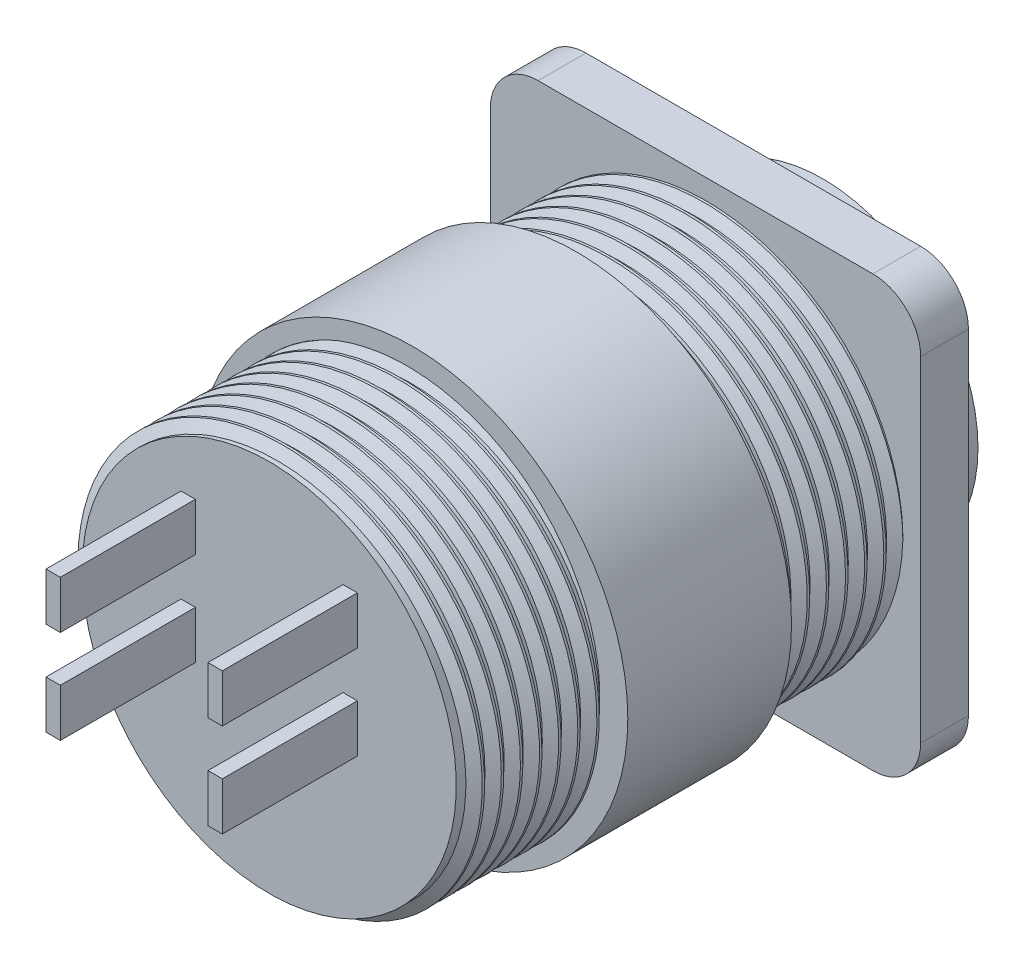
SolidWorks part; units mm, degrees
ref_plane "Front Plane" through (0, 0, 0) normal (0, 0, 1) x (1, 0, 0)
ref_plane "Top Plane" through (0, 0, 0) normal (0, 1, 0) x (1, 0, 0)
ref_plane "Right Plane" through (0, 0, 0) normal (1, 0, 0) x (0, 0, -1)
sketch "Sketch1" plane through (0, 0, 0) normal (0, 0, 1) x (1, 0, 0)
  circle A0 centre (0, 0) radius 7.825
  circle A2 centre (0, 0) radius 6.5
  dimension "D1" = 15.65
  dimension "D2" = 13
extrude "Boss-Extrude1" add sketch "Sketch1" along normal blind 18.25 contours A2 | A0 A2 | A2 | A0 region at (-7.6037, 0, 0) region at (0, 0, 0)
extrude "Boss-Extrude2" add sketch "Sketch1<3>" against normal blind 4.9 contours A2 region at (0, 0, 0)
sketch "Sketch1<3>" plane through (0, 0, 0) normal (0, 0, 1) x (1, 0, 0) same geometry as "Sketch1"
sketch "Sketch2" plane through (0, 0, 0) normal (0, 0, 1) x (1, 0, 0)
  line L1 (9, -9) -> (-9, -9)
  line L2 (9, -9) -> (9, 9)
  line L3 (9, 9) -> (-9, 9)
  line L4 (-9, -9) -> (-9, 9)
  line L5 (9, -9) -> (-9, 9) construction
  line L6 (9, 9) -> (-9, -9) construction
  point P0 (0, 0)
  dimension "D1" = 18
extrude "Boss-Extrude3" add sketch "Sketch2" against normal blind 2
thread "Thread2" pitch 0.8 method extrude profile "Thread Profile2" start angle 0, offset 0, length 0, pitch 0.8, diameter 15.65
ref_plane "Plane5" through (-7.825, 0, 18.25) normal (0, -1, 0) x (-1, 0, 0)
sketch "Thread Profile2" plane through (-7.825, 0, 18.25) normal (0, -1, 0) x (-1, 0, 0)
  line L0 (0, 0) -> (0, 0.8) construction
  line L1 (0, 0) -> (0.433, 0.25)
  line L2 (0.433, 0.25) -> (0.433, 0.35)
  line L3 (0.433, 0.35) -> (0, 0.6)
  line L4 (0.433, 0.3) -> (0, 0.3) construction
  line L11 (0, 0) -> (0, 0.6)
  point P2 (0, 0)
  dimension "Pitch" = 0.8
  dimension "Profile_Angle" = 60
  dimension "Profile_Land" = 0.1
  dimension "Profile_Height" = 0.433
sketch "Sketch12" plane through (0, 0, 18.25) normal (0, 0, 1) x (1, 0, 0)
  circle A0 centre (0, 0) radius 7.825
  circle A1 centre (0, 0) radius 9
  circle A5 centre (0, 0) radius 7.825 construction
  dimension "D1" = 18
extrude "Boss-Extrude4" add sketch "Sketch12" against normal blind 6.85 from offset 6 offset against normal yes
fillet "Fillet1" radius 2 4 edges at (-9, 9, -1) (-9, -9, -1) (9, -9, -1) (9, 9, -1)
sketch "Sketch13" plane through (0, 0, 18.25) normal (0, 0, 1) x (1, 0, 0)
  line L0 (0, 0) -> (0, 7.825) construction
  line L1 (-7.825, 0) -> (7.825, 0) construction
  line L2 (0, 3.9125) -> (-6.7766, 3.9125) construction
  line L3 (-3.3883, 3.9125) -> (-3.3883, 0) construction
  line L4 (-3.6883, 4.9125) -> (-3.0883, 4.9125)
  line L5 (-3.6883, 4.9125) -> (-3.6883, 2.9125)
  line L6 (-3.6883, 2.9125) -> (-3.0883, 2.9125)
  line L7 (-3.0883, 4.9125) -> (-3.0883, 2.9125)
  line L8 (-3.6883, 4.9125) -> (-3.0883, 2.9125) construction
  line L9 (-3.6883, 2.9125) -> (-3.0883, 4.9125) construction
  line L10 (-3.3883, 1.9563) -> (-7.5765, 1.9563) construction
  line L11 (-3.6883, 1) -> (-3.0883, 1)
  line L12 (-3.0883, -1) -> (-3.0883, 1)
  line L13 (-3.6883, -1) -> (-3.0883, -1)
  line L14 (-3.6883, -1) -> (-3.6883, 1)
  line L15 (3.6883, 2.9125) -> (3.0883, 2.9125)
  line L16 (3.0883, 4.9125) -> (3.0883, 2.9125)
  line L17 (3.6883, 4.9125) -> (3.0883, 4.9125)
  line L18 (3.6883, 4.9125) -> (3.6883, 2.9125)
  line L19 (3.6883, -1) -> (3.6883, 1)
  line L20 (3.6883, -1) -> (3.0883, -1)
  line L21 (3.0883, -1) -> (3.0883, 1)
  line L22 (3.6883, 1) -> (3.0883, 1)
  circle A0 centre (0, 0) radius 7.825 construction
  point P8 (0, 0)
  point P10 (-3.3883, 3.9125)
  dimension "D1" = 0.6
  dimension "D2" = 2
extrude "Boss-Extrude5" add sketch "Sketch13" along normal blind 5.65 contours L21 L20 L19 L1 | L19 L22 L21 L1 | L18 L17 L16 L15 | L7 L4 L5 L6 | L14 L1 L12 L11 | L14 L13 L12 L1 region at (-3.3883, 3.9125, 18.25) region at (-3.3883, 0, 18.25) region at (3.3883, 3.9125, 18.25) region at (3.3883, 0, 18.25)
